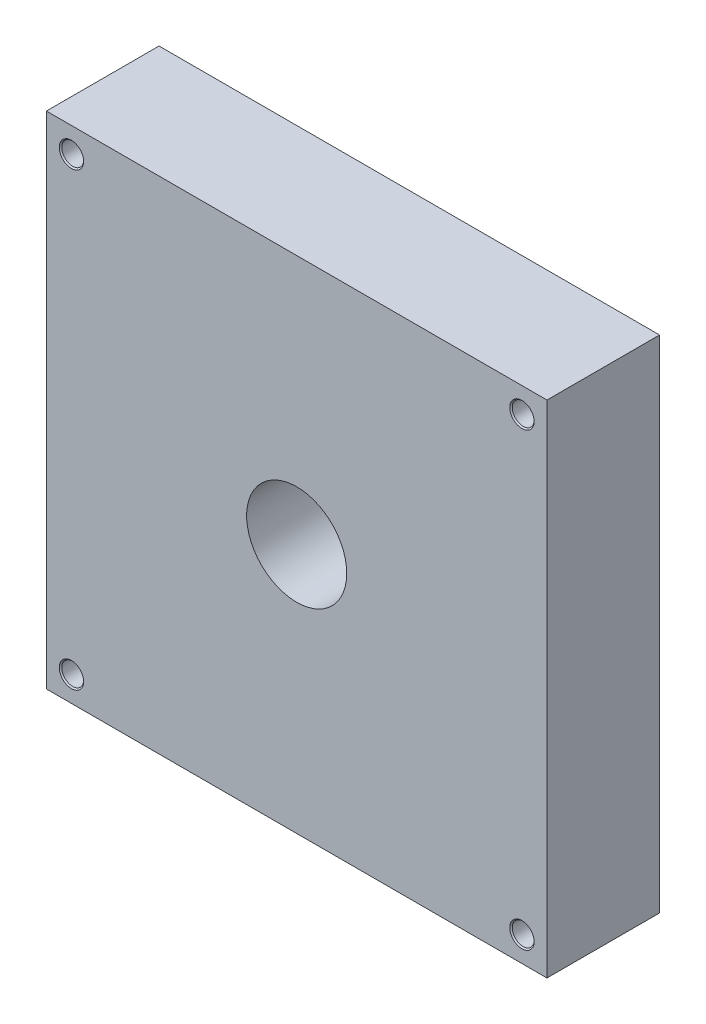
SolidWorks part; units mm, degrees
material "6061-T6 (SS)"
ref_plane "Front Plane" through (0, 0, 0) normal (0, 0, 1) x (1, 0, 0)
ref_plane "Top Plane" through (0, 0, 0) normal (0, 1, 0) x (1, 0, 0)
ref_plane "Right Plane" through (0, 0, 0) normal (1, 0, 0) x (0, 0, -1)
sketch "Sketch1" plane through (0, 0, 0) normal (0, 0, 1) x (1, 0, 0)
  line L1 (127, 127) -> (-127, 127)
  line L2 (127, 127) -> (127, -127)
  line L3 (127, -127) -> (-127, -127)
  line L4 (-127, 127) -> (-127, -127)
  line L5 (127, 127) -> (-127, -127) construction
  line L6 (127, -127) -> (-127, 127) construction
  line L7 (114.3, 114.3) -> (-114.3, 114.3) construction
  line L8 (114.3, 114.3) -> (114.3, -114.3) construction
  line L9 (114.3, -114.3) -> (-114.3, -114.3) construction
  line L10 (-114.3, 114.3) -> (-114.3, -114.3) construction
  line L11 (0, -114.3) -> (0, 114.3) construction
  line L12 (114.3, 0) -> (-114.3, 0) construction
  circle A0 centre (0, 0) radius 127
  circle A1 centre (0, 0) radius 25.4
  point P0 (0, 0)
  dimension "D3" = 50.8
  dimension "D1" = 254
  dimension "D2" = 228.6
extrude "Boss-Extrude1" add sketch "Sketch1" against normal blind 57.15 contours A0 L1 L4 | A0 A1 | A0 L4 L3 | A0 L3 L2 | A0 L2 L1 region at (98.6323, 98.6323, 0) region at (-98.6323, 98.6323, 0) region at (87.2626, 87.2626, 0) region at (98.6323, -98.6323, 0) region at (-98.6323, -98.6323, 0)
hole_wizard "CBORE for 1/4 Socket Head Cap Screw2" positions "Sketch2" profile "Sketch3" counterbore size "1/4" standard "ANSI Inch" end condition through all
sketch "Sketch2" plane through (0, 0, 0) normal (0, 0, 1) x (1, 0, 0)
  point P0 (-114.3, 114.3)
  point P3 (114.3, 114.3)
  point P6 (114.3, -114.3)
  point P9 (-114.3, -114.3)
sketch "Sketch3" plane through (-114.3, 114.3, 0) normal (1, 0, 0) x (0, -1, 0)
  line L0 (0, 0) -> (0, 57.15)
  line L1 (3.2639, 56.515) -> (3.8989, 57.15)
  line L2 (5.5562, 50.8) -> (3.2639, 50.8)
  line L3 (3.2639, 50.8) -> (3.2639, 56.515)
  line L5 (5.5562, 50.8) -> (5.5562, 0.635)
  line L6 (5.5562, 0.635) -> (6.1913, 0)
  line L7 (6.1913, 0) -> (0, 0)
  line L8 (-5.5562, 0.635) -> (-6.1913, 0) construction
  line L11 (0, -6.35) -> (0, 107.95) construction
  line L12 (3.8989, 57.15) -> (0, 57.15)
  line L13 (-3.2639, 56.515) -> (-3.8989, 57.15) construction
  dimension "Thru Hole Dia." = 6.5278
  dimension "Thru Hole Depth" = 57.15
  dimension "C'Bore Dia." = 11.1125
  dimension "C'Bore Depth" = 50.8
  dimension "Near C'Sink Dia." = 12.3825
  dimension "Near C'Sink Angle" = 90
  dimension "Far C'Sink Dia." = 7.7978
  dimension "Far C'Sink Angle" = 90
